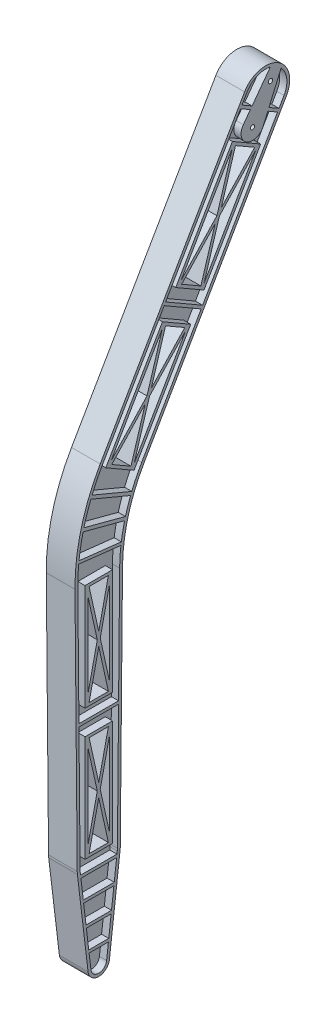
SolidWorks part; units mm, degrees
material "PET"
ref_plane "Front Plane" through (0, 0, 0) normal (0, 0, 1) x (1, 0, 0)
ref_plane "Top Plane" through (0, 0, 0) normal (0, 1, 0) x (1, 0, 0)
ref_plane "Right Plane" through (0, 0, 0) normal (1, 0, 0) x (0, 0, -1)
sketch "Sketch1" plane through (0, 0, 0) normal (1, 0, 0) x (0, 0, -1)
  line L0 (0, 0) -> (-155, -268.4679) construction
  line L1 (0, 0) -> (-19.4856, 11.25) construction
  line L2 (-155, -268.4679) -> (-174.4856, -257.2179) construction
  line L3 (-174.4856, -257.2179) -> (-19.4856, 11.25)
  line L4 (-19.4856, 11.25) -> (19.4856, -11.25) construction
  line L5 (-174.4856, -257.2179) -> (-135.5144, -279.7179) construction
  line L6 (-135.5144, -279.7179) -> (19.4856, -11.25)
  line L7 (-155, -268.4679) -> (-155, -538.4679) construction
  line L8 (-155, -538.4679) -> (-155, -558.4679) construction
  line L9 (-155, -558.4679) -> (-155, -623.0402) construction
  line L10 (-155, -538.4679) -> (-175, -538.4679) construction
  line L11 (-175, -538.4679) -> (-135, -538.4679) construction
  line L12 (-155, -268.4679) -> (-177.499, -268.2595) construction
  line L13 (-177.499, -268.2595) -> (-132.501, -268.6763) construction
  line L14 (-177.499, -268.2595) -> (-175, -538.4679)
  line L15 (-132.501, -268.6763) -> (-135, -538.4679)
  line L16 (-174.8597, -540.8327) -> (-164.9298, -624.2226)
  line L17 (-135.1403, -540.8327) -> (-145.0702, -624.2226)
  circle A0 centre (0, 0) radius 22.5
  circle A1 centre (-155, -268.4679) radius 22.5
  circle A2 centre (-155, -538.4679) radius 20
  circle A3 centre (-155, -623.0402) radius 10
  dimension "D1" = 45
  dimension "D3" = 45
  dimension "D4" = 155
  dimension "D6" = 40
  dimension "D7" = 20
  dimension "D2" = 310
  dimension "D5" = 270
  dimension "D8" = 150
  dimension "D10" = 84.5723
extrude "Boss-Extrude2" add sketch "Sketch1" along normal blind 20 contours A1 L15 L6 A0 L3 | A1 L6 L15 | A2 L15 L6 A1 L14 | L15 A1 L14 | A0 | A2 | A3 A2 | A3 region at (0, -134.2005, 77.4867) region at (0, -268.4679, 155) region at (0, 0, 0) region at (0, -274.433, 133.1432) region at (0, -402.5013, 155.0053) region at (0, -538.4679, 155) region at (0, -582.6002, 155) region at (0, -623.0402, 155)
fillet "Fillet1" radius 150 1 edges at (10, -274.5933, 132.5558)
fillet "Fillet2" radius 175 1 edges at (10, -268.2595, 177.499)
fillet "Fillet3" [suppressed] radius 50
sketch "Sketch2" plane through (20, 0, 0) normal (1, 0, 0) x (0, 0, -1)
  line L0 (0, 0) -> (11.25, 19.4856) construction
  line L1 (0, 0) -> (5.625, 9.7428) construction
  line L2 (5.625, 9.7428) -> (-6.375, -11.0418) construction
  circle A0 centre (0, 0) radius 22.5
  circle A1 centre (-6.375, -11.0418) radius 1.5
  dimension "D3" = 3
  dimension "D1" = 24
  dimension "D2" = 11.25
sketch "Sketch3" plane through (20, 0, 0) normal (1, 0, 0) x (0, 0, -1)
  circle A0 centre (5.625, 9.7428) radius 1.5
  circle A1 centre (-6.375, -11.0418) radius 1.5
  dimension "D1" = 3
  dimension "D2" = 3
extrude "Cut-Extrude1" cut sketch "Sketch3" against normal through all contours A0
extrude "Cut-Extrude3" cut sketch "Sketch2" against normal through all contours A1
sketch "Sketch4" plane through (20, 0, 0) normal (1, 0, 0) x (0, 0, -1)
  line L0 (-33.4856, -12.9987) -> (5.4856, -35.4987)
  line L1 (-153.6723, -221.1682) -> (-19.4856, 11.25) construction
  line L2 (-112.8314, -240.4297) -> (19.4856, -11.25) construction
  line L3 (-174.9649, -539.6524) -> (-135.0351, -539.6524)
  line L4 (-177.1103, -310.2866) -> (-175, -538.4679) construction
  line L5 (-177.1103, -310.2866) -> (-175, -538.4679)
  line L6 (-153.6723, -221.1682) -> (-33.4856, -12.9987)
  line L7 (-112.8314, -240.4297) -> (5.4856, -35.4987)
  line L8 (-132.9212, -314.0404) -> (-135, -538.4679) construction
  line L9 (-132.9212, -314.0404) -> (-135, -538.4679)
  arc A0 (19.4856, -11.25) -> (-19.4856, 11.25) centre (0, 0) ccw construction
  arc A1 (-175, -538.4679) -> (-174.8597, -540.8327) centre (-155, -538.4679) ccw construction
  arc A2 (-135.1403, -540.8327) -> (-135, -538.4679) centre (-155, -538.4679) ccw construction
  arc A3 (-153.6723, -221.1682) -> (-177.1103, -310.2866) centre (-2.1178, -308.6682) ccw construction
  arc A4 (-153.6723, -221.1682) -> (-177.1103, -310.2866) centre (-2.1178, -308.6682) ccw
  arc A5 (-112.8314, -240.4297) -> (-132.9212, -314.0404) centre (17.0724, -315.4297) ccw construction
  arc A6 (-112.8314, -240.4297) -> (-132.9212, -314.0404) centre (17.0724, -315.4297) ccw
  dimension "D1" = 28
sketch "Sketch5" plane through (20, 0, 0) normal (1, 0, 0) x (0, 0, -1)
  line L0 (-29.8253, -26.659) -> (-8.1747, -39.159)
  line L1 (-29.8253, -26.659) -> (-144.8253, -225.8448)
  line L2 (-8.1747, -39.159) -> (-123.1747, -238.3448)
  line L3 (-144.8253, -225.8448) -> (-123.1747, -238.3448)
  line L4 (-33.4856, -12.9987) -> (5.4856, -35.4987) construction
  line L5 (-112.8314, -240.4297) -> (5.4856, -35.4987) construction
  line L6 (-153.6723, -221.1682) -> (-33.4856, -12.9987) construction
  line L7 (-165.0811, -529.6524) -> (-144.9188, -529.6524)
  line L8 (-165.0811, -529.6524) -> (-165.0811, -314.6524)
  line L9 (-144.9188, -529.6524) -> (-144.9188, -314.6524)
  line L10 (-165.0811, -314.6524) -> (-144.9188, -314.6524)
  line L11 (-174.9649, -539.6524) -> (-135.0351, -539.6524) construction
  line L12 (-132.9212, -314.0404) -> (-135, -538.4679) construction
  line L13 (-177.1103, -310.2866) -> (-175, -538.4679) construction
  dimension "D1" = 10
  dimension "D2" = 10
  dimension "D3" = 10
  dimension "D4" = 230
  dimension "D5" = 10
  dimension "D6" = 10
  dimension "D7" = 10
  dimension "D8" = 215
extrude "Cut-Extrude4" cut sketch "Sketch5" against normal through all
sketch "Sketch6" plane through (20, 0, 0) normal (1, 0, 0) x (0, 0, -1)
  line L6 (-19.4856, 11.25) -> (-153.6723, -221.1682)
  line L7 (-177.1103, -310.2866) -> (-175, -538.4679)
  line L8 (-174.8597, -540.8327) -> (-164.9298, -624.2226)
  line L9 (-145.0702, -624.2226) -> (-135.1403, -540.8327)
  line L10 (-135, -538.4679) -> (-132.9212, -314.0404)
  line L11 (-112.8314, -240.4297) -> (19.4856, -11.25)
  line L12 (-19.4856, 11.25) -> (-153.6723, -221.1682)
  line L13 (-177.1103, -310.2866) -> (-175, -538.4679)
  line L14 (-174.8597, -540.8327) -> (-164.9298, -624.2226)
  line L15 (-145.0702, -624.2226) -> (-135.1403, -540.8327)
  line L16 (-135, -538.4679) -> (-132.9212, -314.0404)
  line L17 (-112.8314, -240.4297) -> (19.4856, -11.25)
  arc A6 (-153.6723, -221.1682) -> (-177.1103, -310.2866) centre (-2.1178, -308.6682) ccw
  arc A7 (-175, -538.4679) -> (-174.8597, -540.8327) centre (-155, -538.4679) ccw
  arc A8 (-164.9298, -624.2226) -> (-145.0702, -624.2226) centre (-155, -623.0402) ccw
  arc A9 (-135.1403, -540.8327) -> (-135, -538.4679) centre (-155, -538.4679) ccw
  arc A10 (-112.8314, -240.4297) -> (-132.9212, -314.0404) centre (17.0724, -315.4297) ccw
  arc A11 (19.4856, -11.25) -> (-19.4856, 11.25) centre (0, 0) ccw
  arc A12 (-153.6723, -221.1682) -> (-177.1103, -310.2866) centre (-2.1178, -308.6682) ccw
  arc A13 (-175, -538.4679) -> (-174.8597, -540.8327) centre (-155, -538.4679) ccw
  arc A14 (-164.9298, -624.2226) -> (-145.0702, -624.2226) centre (-155, -623.0402) ccw
  arc A15 (-135.1403, -540.8327) -> (-135, -538.4679) centre (-155, -538.4679) ccw
  arc A16 (-112.8314, -240.4297) -> (-132.9212, -314.0404) centre (17.0724, -315.4297) ccw
  arc A17 (19.4856, -11.25) -> (-19.4856, 11.25) centre (0, 0) ccw
  dimension "D1" = 0
scale "Scale1" scale about centroid uniform scaling yes scale factor 0.75
sketch "Sketch7" plane through (17.5, 0, 0) normal (1, 0, 0) x (0, 0, -1)
  line L0 (-42.9814, -81.6568) -> (-30.5187, -88.8521)
  line L1 (-42.9814, -81.6568) -> (-29.8288, -58.8759)
  line L2 (-30.5187, -88.8521) -> (-17.3662, -66.0713)
  line L3 (-29.8288, -58.8759) -> (-17.3662, -66.0713)
  line L4 (-143.9105, -238.1692) -> (-43.2705, -63.8556) construction
  line L5 (-34.7873, -101.6623) -> (-51.0253, -92.2873) construction
  dimension "D1" = 14.3906
  dimension "D2" = 26.3051
  dimension "D3" = 13.2282
  dimension "D4" = 9.151
extrude "Boss-Extrude3" add sketch "Sketch7" against normal through all
sketch "Sketch8" plane through (17.5, 0, 0) normal (1, 0, 0) x (0, 0, -1)
  line L0 (-42.9063, -96.9748) -> (-20.2188, -57.6789) construction
  line L1 (-34.7873, -101.6623) -> (-51.0253, -92.2873) construction
  circle A0 centre (-25.2188, -66.3391) radius 1.5
  circle A1 centre (-37.7188, -87.9898) radius 1.5
  arc A2 (-14.0421, -80.7306) -> (-43.2705, -63.8556) centre (-28.6563, -72.2931) ccw construction
  dimension "D3" = 3
  dimension "D4" = 3
  dimension "D1" = 25
  dimension "D2" = 10
extrude "Cut-Extrude5" cut sketch "Sketch8" against normal through all
sketch "Sketch9" plane through (0, 2.7728, 4.8026) normal (0, 0.5, 0.866) x (1, 0, 0)
  line L0 (17.5, -278.2159) -> (17.5, -76.9358) construction
  line L1 (17.5, -60.0608) -> (12.5, -60.0608)
  line L2 (17.5, -60.0608) -> (17.5, -547.2373)
  line L3 (17.5, -547.2373) -> (12.5, -547.2373)
  line L4 (12.5, -60.0608) -> (12.5, -547.2373)
  line L5 (2.5, -278.2159) -> (2.5, -76.9358) construction
  line L6 (17.5, -60.0608) -> (2.5, -60.0608) construction
  line L7 (2.5, -547.2373) -> (17.5, -547.2373) construction
  dimension "D1" = 10
extrude "Cut-Extrude6" cut sketch "Sketch9" against normal through all
sketch "Sketch11" plane through (12.5, 0, 0) normal (1, 0, 0) x (0, 0, -1)
  line L0 (-137.2753, -241.6767) -> (-121.0373, -251.0517)
  line L1 (-137.2753, -241.6767) -> (-51.0253, -92.2873)
  line L2 (-121.0373, -251.0517) -> (-34.7873, -101.6623)
  line L3 (-51.0253, -92.2873) -> (-34.7873, -101.6623)
  line L4 (-34.7873, -101.6623) -> (-51.0253, -92.2873) construction
  line L5 (-152.4672, -308.2823) -> (-137.3454, -308.2823)
  line L6 (-152.4672, -308.2823) -> (-152.4672, -469.5323)
  line L7 (-137.3454, -308.2823) -> (-137.3454, -469.5323)
  line L8 (-152.4672, -469.5323) -> (-137.3454, -469.5323)
  line L9 (-152.4672, -469.5323) -> (-137.3454, -469.5323) construction
extrude "Boss-Extrude4" add sketch "Sketch11" against normal blind 10
sketch "Sketch13" plane through (12.5, 0, 0) normal (1, 0, 0) x (0, 0, -1)
  line L0 (-137.2753, -241.6767) -> (-121.0373, -251.0517)
  line L1 (-137.2753, -241.6767) -> (-99.7753, -176.7248)
  line L2 (-121.0373, -251.0517) -> (-83.5373, -186.0998)
  line L3 (-99.7753, -176.7248) -> (-83.5373, -186.0998)
  line L4 (-152.4672, -399.5323) -> (-137.3454, -399.5323)
  line L5 (-152.4672, -399.5323) -> (-152.4672, -469.5323)
  line L6 (-137.3454, -399.5323) -> (-137.3454, -469.5323)
  line L7 (-152.4672, -469.5323) -> (-137.3454, -469.5323)
  line L9 (-152.4672, -469.5323) -> (-137.3454, -469.5323) construction
  line L10 (-152.4672, -308.2823) -> (-152.4672, -469.5323) construction
  line L11 (-137.3454, -308.2823) -> (-137.3454, -469.5323) construction
  line L13 (-137.2753, -241.6767) -> (-51.0253, -92.2873) construction
  line L16 (-121.0373, -251.0517) -> (-34.7873, -101.6623) construction
  line L17 (-137.2753, -241.6767) -> (-121.0373, -251.0517) construction
  line L18 (-51.0253, -92.2873) -> (-34.7873, -101.6623)
  line L19 (-51.0253, -92.2873) -> (-88.5253, -157.2392)
  line L20 (-34.7873, -101.6623) -> (-72.2873, -166.6142)
  line L21 (-88.5253, -157.2392) -> (-72.2873, -166.6142)
  line L22 (-152.4672, -308.2823) -> (-137.3454, -308.2823)
  line L23 (-152.4672, -308.2823) -> (-152.4672, -378.2823)
  line L24 (-137.3454, -308.2823) -> (-137.3454, -378.2823)
  line L25 (-152.4672, -378.2823) -> (-137.3454, -378.2823)
  dimension "D1" = 75
  dimension "D2" = 75
  dimension "D3" = 70
  dimension "D4" = 70
extrude "Cut-Extrude7" cut sketch "Sketch13" against normal blind 10
ref_plane "Plane1" through (0, -450.9942, -148.3609) normal (0, -0.9499, -0.3125) x (-1, 0, 0)
sketch "Sketch15" plane through (12.5, 0, 0) normal (1, 0, 0) x (0, 0, -1)
  line L0 (-25.2188, -66.3391) -> (-37.7188, -87.9898) construction
  point P4 (0, 0)
ref_plane "Plane2" through (0, -13.4953, 41.0235) normal (0, -0.3125, 0.9499) x (1, 0, 0)
sketch "Sketch16" plane through (12.5, 0, 0) normal (1, 0, 0) x (0, 0, -1)
  line L0 (-144.9063, -547.0732) -> (-153.3569, -521.3847) construction
  line L1 (140.524, -453.5723) -> (156.1977, -448.4162) construction
  arc A0 (-152.3537, -540.46) -> (-137.4589, -540.46) centre (-144.9063, -539.5732) ccw construction
  dimension "D1" = 90
  dimension "D2" = 27.0428
sketch "Sketch18" plane through (2.5, 0, 0) normal (-1, 0, 0) x (0, 0, 1)
  line L0 (88.5253, -157.2392) -> (72.2873, -166.6142) construction
  line L1 (72.2873, -166.6142) -> (34.7873, -101.6623) construction
  line L2 (51.0253, -92.2873) -> (88.5253, -157.2392) construction
  line L3 (34.7873, -101.6623) -> (51.0253, -92.2873) construction
  line L4 (88.5253, -157.2392) -> (72.2873, -166.6142)
  line L5 (72.2873, -166.6142) -> (34.7873, -101.6623)
  line L6 (159.9063, -476.144) -> (161.4891, -305.008)
  line L7 (143.9105, -238.1692) -> (43.2705, -63.8556)
  line L8 (14.0421, -80.7306) -> (113.2799, -252.6154)
  line L9 (128.3472, -307.8233) -> (129.9063, -476.144)
  line L10 (130.0116, -477.9176) -> (137.4589, -540.46)
  line L11 (152.3537, -540.46) -> (159.8011, -477.9176)
  line L12 (159.9063, -476.144) -> (161.4891, -305.008)
  line L13 (143.9105, -238.1692) -> (43.2705, -63.8556)
  line L14 (14.0421, -80.7306) -> (113.2799, -252.6154)
  line L15 (128.3472, -307.8233) -> (129.9063, -476.144)
  line L16 (130.0116, -477.9176) -> (137.4589, -540.46)
  line L17 (152.3537, -540.46) -> (159.8011, -477.9176)
  line L18 (51.0253, -92.2873) -> (88.5253, -157.2392)
  line L19 (34.7873, -101.6623) -> (51.0253, -92.2873)
  line L20 (137.2753, -241.6767) -> (121.0373, -251.0517) construction
  line L21 (99.7753, -176.7248) -> (137.2753, -241.6767) construction
  line L22 (121.0373, -251.0517) -> (83.5373, -186.0998) construction
  line L23 (83.5373, -186.0998) -> (99.7753, -176.7248) construction
  line L24 (137.2753, -241.6767) -> (121.0373, -251.0517)
  line L25 (99.7753, -176.7248) -> (137.2753, -241.6767)
  line L26 (121.0373, -251.0517) -> (83.5373, -186.0998)
  line L27 (83.5373, -186.0998) -> (99.7753, -176.7248)
  line L28 (137.3454, -308.2823) -> (152.4672, -308.2823) construction
  line L29 (152.4672, -308.2823) -> (152.4672, -378.2823) construction
  line L30 (137.3454, -378.2823) -> (137.3454, -308.2823) construction
  line L31 (152.4672, -378.2823) -> (137.3454, -378.2823) construction
  line L32 (152.4672, -378.2823) -> (137.3454, -378.2823)
  line L33 (137.3454, -378.2823) -> (137.3454, -308.2823)
  line L34 (152.4672, -308.2823) -> (152.4672, -378.2823)
  line L35 (137.3454, -308.2823) -> (152.4672, -308.2823)
  line L36 (152.4672, -469.5323) -> (137.3454, -469.5323) construction
  line L37 (152.4672, -399.5323) -> (152.4672, -469.5323) construction
  line L38 (137.3454, -469.5323) -> (137.3454, -399.5323) construction
  line L39 (137.3454, -399.5323) -> (152.4672, -399.5323) construction
  line L40 (152.4672, -469.5323) -> (137.3454, -469.5323)
  line L41 (152.4672, -399.5323) -> (152.4672, -469.5323)
  line L42 (137.3454, -469.5323) -> (137.3454, -399.5323)
  line L43 (137.3454, -399.5323) -> (152.4672, -399.5323)
  circle A0 centre (25.2188, -66.3391) radius 1.5 construction
  circle A1 centre (37.7188, -87.9898) radius 1.5 construction
  circle A2 centre (25.2188, -66.3391) radius 1.5
  circle A3 centre (37.7188, -87.9898) radius 1.5
  arc A6 (161.4891, -305.008) -> (143.9105, -238.1692) centre (30.2447, -303.7942) ccw
  arc A7 (43.2705, -63.8556) -> (14.0421, -80.7306) centre (28.6563, -72.2931) ccw
  arc A8 (128.3472, -307.8233) -> (113.2799, -252.6154) centre (15.852, -308.8654) ccw
  arc A9 (129.9063, -476.144) -> (130.0116, -477.9176) centre (144.9063, -476.144) ccw
  arc A10 (137.4589, -540.46) -> (152.3537, -540.46) centre (144.9063, -539.5732) ccw
  arc A11 (159.8011, -477.9176) -> (159.9063, -476.144) centre (144.9063, -476.144) ccw
  arc A12 (161.4891, -305.008) -> (143.9105, -238.1692) centre (30.2447, -303.7942) ccw
  arc A13 (43.2705, -63.8556) -> (14.0421, -80.7306) centre (28.6563, -72.2931) ccw
  arc A14 (128.3472, -307.8233) -> (113.2799, -252.6154) centre (15.852, -308.8654) ccw
  arc A15 (129.9063, -476.144) -> (130.0116, -477.9176) centre (144.9063, -476.144) ccw
  arc A16 (137.4589, -540.46) -> (152.3537, -540.46) centre (144.9063, -539.5732) ccw
  arc A17 (159.8011, -477.9176) -> (159.9063, -476.144) centre (144.9063, -476.144) ccw
  dimension "D1" = 0
extrude "Boss-Extrude5" add sketch "Sketch18" along normal blind 5
sketch "Sketch19" plane through (-2.5, 0, 0) normal (-1, 0, 0) x (0, 0, 1)
  line L46 (131.9975, -477.6811) -> (139.4449, -540.2236)
  line L47 (150.3677, -540.2236) -> (157.8151, -477.6811)
  line L48 (157.9063, -476.1351) -> (159.4892, -304.9895)
  line L49 (130.3471, -307.8048) -> (131.9063, -476.135)
  line L50 (142.1785, -239.1692) -> (41.5385, -64.8556)
  line L51 (15.7742, -79.7306) -> (115.0119, -251.6154)
  line L52 (131.9975, -477.6811) -> (139.4449, -540.2236)
  line L53 (150.3677, -540.2236) -> (157.8151, -477.6811)
  line L54 (157.9063, -476.1351) -> (159.4892, -304.9895)
  line L55 (130.3471, -307.8048) -> (131.9063, -476.135)
  line L56 (142.1785, -239.1692) -> (41.5385, -64.8556)
  line L57 (15.7742, -79.7306) -> (115.0119, -251.6154)
  line L60 (71.5553, -169.3462) -> (91.2574, -157.9712)
  line L61 (32.0553, -100.9302) -> (71.5553, -169.3462)
  line L62 (91.2574, -157.9712) -> (51.7574, -89.5552)
  line L63 (51.7574, -89.5552) -> (32.0553, -100.9302)
  line L64 (71.5553, -169.3462) -> (91.2574, -157.9712)
  line L65 (32.0553, -100.9302) -> (71.5553, -169.3462)
  line L66 (91.2574, -157.9712) -> (51.7574, -89.5552)
  line L67 (51.7574, -89.5552) -> (32.0553, -100.9302)
  line L72 (100.5074, -173.9927) -> (80.8053, -185.3677)
  line L73 (80.8053, -185.3677) -> (120.3053, -253.7837)
  line L74 (140.0074, -242.4087) -> (100.5074, -173.9927)
  line L75 (120.3053, -253.7837) -> (140.0074, -242.4087)
  line L76 (100.5074, -173.9927) -> (80.8053, -185.3677)
  line L77 (80.8053, -185.3677) -> (120.3053, -253.7837)
  line L78 (140.0074, -242.4087) -> (100.5074, -173.9927)
  line L79 (120.3053, -253.7837) -> (140.0074, -242.4087)
  line L84 (154.4672, -306.2823) -> (135.3454, -306.2823)
  line L85 (154.4672, -380.2823) -> (154.4672, -306.2823)
  line L86 (135.3454, -306.2823) -> (135.3454, -380.2823)
  line L87 (135.3454, -380.2823) -> (154.4672, -380.2823)
  line L88 (154.4672, -306.2823) -> (135.3454, -306.2823)
  line L89 (154.4672, -380.2823) -> (154.4672, -306.2823)
  line L90 (135.3454, -306.2823) -> (135.3454, -380.2823)
  line L91 (135.3454, -380.2823) -> (154.4672, -380.2823)
  line L96 (154.4672, -471.5323) -> (154.4672, -397.5323)
  line L97 (135.3454, -471.5323) -> (154.4672, -471.5323)
  line L98 (135.3454, -397.5323) -> (135.3454, -471.5323)
  line L99 (154.4672, -397.5323) -> (135.3454, -397.5323)
  line L100 (154.4672, -471.5323) -> (154.4672, -397.5323)
  line L101 (135.3454, -471.5323) -> (154.4672, -471.5323)
  line L102 (135.3454, -397.5323) -> (135.3454, -471.5323)
  line L103 (154.4672, -397.5323) -> (135.3454, -397.5323)
  arc A46 (139.4449, -540.2236) -> (150.3677, -540.2236) centre (144.9063, -539.5732) ccw
  arc A47 (157.8151, -477.6811) -> (157.9063, -476.1351) centre (144.9063, -476.144) ccw
  arc A48 (131.9063, -476.135) -> (131.9975, -477.6811) centre (144.9063, -476.144) ccw
  arc A49 (159.4892, -304.9895) -> (142.1785, -239.1692) centre (30.2447, -303.7942) ccw
  arc A50 (130.3471, -307.8048) -> (115.0119, -251.6154) centre (15.852, -308.8654) ccw
  arc A51 (41.5385, -64.8556) -> (15.7742, -79.7306) centre (28.6563, -72.2931) ccw
  arc A52 (139.4449, -540.2236) -> (150.3677, -540.2236) centre (144.9063, -539.5732) ccw
  arc A53 (157.8151, -477.6811) -> (157.9063, -476.1351) centre (144.9063, -476.144) ccw
  arc A54 (131.9063, -476.135) -> (131.9975, -477.6811) centre (144.9063, -476.144) ccw
  arc A55 (159.4892, -304.9895) -> (142.1785, -239.1692) centre (30.2447, -303.7942) ccw
  arc A56 (130.3471, -307.8048) -> (115.0119, -251.6154) centre (15.852, -308.8654) ccw
  arc A57 (41.5385, -64.8556) -> (15.7742, -79.7306) centre (28.6563, -72.2931) ccw
  circle A61 centre (25.2188, -66.3391) radius 3.5
  circle A62 centre (25.2188, -66.3391) radius 3.5
  circle A64 centre (37.7188, -87.9898) radius 3.5
  circle A65 centre (37.7188, -87.9898) radius 3.5
  dimension "D1" = 2
  dimension "D2" = 2
  dimension "D3" = 2
  dimension "D4" = 2
  dimension "D5" = 2
  dimension "D6" = 2
  dimension "D7" = 2
extrude "Cut-Extrude8" cut sketch "Sketch19" against normal blind 5
sketch "Sketch21" plane through (12.5, 0, 0) normal (1, 0, 0) x (0, 0, -1)
  line L0 (-137.2753, -241.6767) -> (-121.0373, -251.0517) construction
  line L1 (-99.7753, -176.7248) -> (-137.2753, -241.6767) construction
  line L2 (-121.0373, -251.0517) -> (-83.5373, -186.0998) construction
  line L3 (-83.5373, -186.0998) -> (-99.7753, -176.7248) construction
  line L4 (-137.2753, -241.6767) -> (-121.0373, -251.0517)
  line L5 (-99.7753, -176.7248) -> (-137.2753, -241.6767)
  line L6 (-43.2705, -63.8556) -> (-143.9105, -238.1692)
  line L7 (-161.4891, -305.008) -> (-159.9063, -476.144)
  line L8 (-159.8011, -477.9176) -> (-152.3537, -540.46)
  line L9 (-137.4589, -540.46) -> (-130.0116, -477.9176)
  line L10 (-129.9063, -476.144) -> (-128.3472, -307.8233)
  line L11 (-113.2799, -252.6154) -> (-14.0421, -80.7306)
  line L12 (-43.2705, -63.8556) -> (-143.9105, -238.1692)
  line L13 (-161.4891, -305.008) -> (-159.9063, -476.144)
  line L14 (-159.8011, -477.9176) -> (-152.3537, -540.46)
  line L15 (-137.4589, -540.46) -> (-130.0116, -477.9176)
  line L16 (-129.9063, -476.144) -> (-128.3472, -307.8233)
  line L17 (-113.2799, -252.6154) -> (-14.0421, -80.7306)
  line L18 (-121.0373, -251.0517) -> (-83.5373, -186.0998)
  line L19 (-83.5373, -186.0998) -> (-99.7753, -176.7248)
  line L20 (-72.2873, -166.6142) -> (-34.7873, -101.6623) construction
  line L21 (-51.0253, -92.2873) -> (-88.5253, -157.2392) construction
  line L22 (-34.7873, -101.6623) -> (-51.0253, -92.2873) construction
  line L23 (-88.5253, -157.2392) -> (-72.2873, -166.6142) construction
  line L24 (-88.5253, -157.2392) -> (-72.2873, -166.6142)
  line L25 (-72.2873, -166.6142) -> (-34.7873, -101.6623)
  line L26 (-34.7873, -101.6623) -> (-51.0253, -92.2873)
  line L27 (-51.0253, -92.2873) -> (-88.5253, -157.2392)
  line L28 (-152.4672, -308.2823) -> (-152.4672, -378.2823) construction
  line L29 (-137.3454, -378.2823) -> (-137.3454, -308.2823) construction
  line L30 (-152.4672, -378.2823) -> (-137.3454, -378.2823) construction
  line L31 (-137.3454, -308.2823) -> (-152.4672, -308.2823) construction
  line L32 (-152.4672, -378.2823) -> (-137.3454, -378.2823)
  line L33 (-137.3454, -378.2823) -> (-137.3454, -308.2823)
  line L34 (-137.3454, -308.2823) -> (-152.4672, -308.2823)
  line L35 (-152.4672, -308.2823) -> (-152.4672, -378.2823)
  line L36 (-137.3454, -399.5323) -> (-152.4672, -399.5323) construction
  line L37 (-152.4672, -399.5323) -> (-152.4672, -469.5323) construction
  line L38 (-137.3454, -469.5323) -> (-137.3454, -399.5323) construction
  line L39 (-152.4672, -469.5323) -> (-137.3454, -469.5323) construction
  line L40 (-137.3454, -399.5323) -> (-152.4672, -399.5323)
  line L41 (-152.4672, -399.5323) -> (-152.4672, -469.5323)
  line L42 (-137.3454, -469.5323) -> (-137.3454, -399.5323)
  line L43 (-152.4672, -469.5323) -> (-137.3454, -469.5323)
  circle A0 centre (-25.2188, -66.3391) radius 1.5 construction
  circle A1 centre (-37.7188, -87.9898) radius 1.5 construction
  circle A2 centre (-25.2188, -66.3391) radius 1.5
  circle A3 centre (-37.7188, -87.9898) radius 1.5
  arc A6 (-143.9105, -238.1692) -> (-161.4891, -305.008) centre (-30.2447, -303.7942) ccw
  arc A7 (-159.9063, -476.144) -> (-159.8011, -477.9176) centre (-144.9063, -476.144) ccw
  arc A8 (-152.3537, -540.46) -> (-137.4589, -540.46) centre (-144.9063, -539.5732) ccw
  arc A9 (-130.0116, -477.9176) -> (-129.9063, -476.144) centre (-144.9063, -476.144) ccw
  arc A10 (-113.2799, -252.6154) -> (-128.3472, -307.8233) centre (-15.852, -308.8654) ccw
  arc A11 (-14.0421, -80.7306) -> (-43.2705, -63.8556) centre (-28.6563, -72.2931) ccw
  arc A12 (-143.9105, -238.1692) -> (-161.4891, -305.008) centre (-30.2447, -303.7942) ccw
  arc A13 (-159.9063, -476.144) -> (-159.8011, -477.9176) centre (-144.9063, -476.144) ccw
  arc A14 (-152.3537, -540.46) -> (-137.4589, -540.46) centre (-144.9063, -539.5732) ccw
  arc A15 (-130.0116, -477.9176) -> (-129.9063, -476.144) centre (-144.9063, -476.144) ccw
  arc A16 (-113.2799, -252.6154) -> (-128.3472, -307.8233) centre (-15.852, -308.8654) ccw
  arc A17 (-14.0421, -80.7306) -> (-43.2705, -63.8556) centre (-28.6563, -72.2931) ccw
  dimension "D1" = 0
extrude "Boss-Extrude6" add sketch "Sketch21" along normal blind 5
sketch "Sketch22" plane through (17.5, 0, 0) normal (1, 0, 0) x (0, 0, -1)
  line L45 (-157.8151, -477.6811) -> (-150.3677, -540.2236)
  line L46 (-139.4449, -540.2236) -> (-131.9975, -477.6811)
  line L47 (-131.9063, -476.135) -> (-130.3471, -307.8048)
  line L48 (-159.4892, -304.9895) -> (-157.9063, -476.1351)
  line L49 (-115.0119, -251.6154) -> (-15.7742, -79.7306)
  line L50 (-41.5385, -64.8556) -> (-142.1785, -239.1692)
  line L51 (-157.8151, -477.6811) -> (-150.3677, -540.2236)
  line L52 (-139.4449, -540.2236) -> (-131.9975, -477.6811)
  line L53 (-131.9063, -476.135) -> (-130.3471, -307.8048)
  line L54 (-159.4892, -304.9895) -> (-157.9063, -476.1351)
  line L55 (-115.0119, -251.6154) -> (-15.7742, -79.7306)
  line L56 (-41.5385, -64.8556) -> (-142.1785, -239.1692)
  line L65 (-91.2574, -157.9712) -> (-71.5553, -169.3462)
  line L66 (-71.5553, -169.3462) -> (-32.0553, -100.9302)
  line L67 (-32.0553, -100.9302) -> (-51.7574, -89.5552)
  line L68 (-51.7574, -89.5552) -> (-91.2574, -157.9712)
  line L69 (-91.2574, -157.9712) -> (-71.5553, -169.3462)
  line L70 (-71.5553, -169.3462) -> (-32.0553, -100.9302)
  line L71 (-32.0553, -100.9302) -> (-51.7574, -89.5552)
  line L72 (-51.7574, -89.5552) -> (-91.2574, -157.9712)
  line L83 (-140.0074, -242.4087) -> (-120.3053, -253.7837)
  line L84 (-100.5074, -173.9927) -> (-140.0074, -242.4087)
  line L85 (-120.3053, -253.7837) -> (-80.8053, -185.3677)
  line L86 (-80.8053, -185.3677) -> (-100.5074, -173.9927)
  line L87 (-140.0074, -242.4087) -> (-120.3053, -253.7837)
  line L88 (-100.5074, -173.9927) -> (-140.0074, -242.4087)
  line L89 (-120.3053, -253.7837) -> (-80.8053, -185.3677)
  line L90 (-80.8053, -185.3677) -> (-100.5074, -173.9927)
  line L104 (-154.4672, -380.2823) -> (-135.3454, -380.2823)
  line L105 (-154.4672, -306.2823) -> (-154.4672, -380.2823)
  line L106 (-135.3454, -306.2823) -> (-154.4672, -306.2823)
  line L107 (-135.3454, -380.2823) -> (-135.3454, -306.2823)
  line L108 (-154.4672, -380.2823) -> (-135.3454, -380.2823)
  line L109 (-154.4672, -306.2823) -> (-154.4672, -380.2823)
  line L110 (-135.3454, -306.2823) -> (-154.4672, -306.2823)
  line L111 (-135.3454, -380.2823) -> (-135.3454, -306.2823)
  line L122 (-154.4672, -471.5323) -> (-135.3454, -471.5323)
  line L123 (-135.3454, -471.5323) -> (-135.3454, -397.5323)
  line L124 (-135.3454, -397.5323) -> (-154.4672, -397.5323)
  line L125 (-154.4672, -397.5323) -> (-154.4672, -471.5323)
  line L126 (-154.4672, -471.5323) -> (-135.3454, -471.5323)
  line L127 (-135.3454, -471.5323) -> (-135.3454, -397.5323)
  line L128 (-135.3454, -397.5323) -> (-154.4672, -397.5323)
  line L129 (-154.4672, -397.5323) -> (-154.4672, -471.5323)
  arc A45 (-150.3677, -540.2236) -> (-139.4449, -540.2236) centre (-144.9063, -539.5732) ccw
  arc A46 (-131.9975, -477.6811) -> (-131.9063, -476.135) centre (-144.9063, -476.144) ccw
  arc A47 (-157.9063, -476.1351) -> (-157.8151, -477.6811) centre (-144.9063, -476.144) ccw
  arc A48 (-115.0119, -251.6154) -> (-130.3471, -307.8048) centre (-15.852, -308.8654) ccw
  arc A49 (-142.1785, -239.1692) -> (-159.4892, -304.9895) centre (-30.2447, -303.7942) ccw
  arc A50 (-15.7742, -79.7306) -> (-41.5385, -64.8556) centre (-28.6563, -72.2931) ccw
  arc A51 (-150.3677, -540.2236) -> (-139.4449, -540.2236) centre (-144.9063, -539.5732) ccw
  arc A52 (-131.9975, -477.6811) -> (-131.9063, -476.135) centre (-144.9063, -476.144) ccw
  arc A53 (-157.9063, -476.1351) -> (-157.8151, -477.6811) centre (-144.9063, -476.144) ccw
  arc A54 (-115.0119, -251.6154) -> (-130.3471, -307.8048) centre (-15.852, -308.8654) ccw
  arc A55 (-142.1785, -239.1692) -> (-159.4892, -304.9895) centre (-30.2447, -303.7942) ccw
  arc A56 (-15.7742, -79.7306) -> (-41.5385, -64.8556) centre (-28.6563, -72.2931) ccw
  circle A59 centre (-25.2188, -66.3391) radius 3.5
  circle A60 centre (-25.2188, -66.3391) radius 3.5
  circle A62 centre (-37.7188, -87.9898) radius 3.5
  circle A63 centre (-37.7188, -87.9898) radius 3.5
  dimension "D1" = 2
  dimension "D2" = 2
  dimension "D3" = 2
  dimension "D4" = 2
  dimension "D5" = 2
  dimension "D6" = 2
  dimension "D7" = 2
extrude "Cut-Extrude9" cut sketch "Sketch22" against normal blind 5
sketch "Sketch24" plane through (12.5, 0, 0) normal (1, 0, 0) x (0, 0, -1)
  line L0 (-46.0385, -72.6498) -> (-20.2742, -87.5248)
  line L1 (-41.5385, -64.8556) -> (-142.1785, -239.1692) construction
  line L2 (-115.0119, -251.6154) -> (-15.7742, -79.7306) construction
  line L3 (-45.0385, -70.9177) -> (-19.2742, -85.7927)
  line L4 (-41.5385, -64.8556) -> (-142.1785, -239.1692) construction
  line L5 (-32.0553, -100.9302) -> (-51.7574, -89.5552) construction
  line L6 (-155.3388, -271.2823) -> (-126.3395, -278.8193)
  line L7 (-156.5965, -276.1216) -> (-154.0811, -266.4431) construction
  line L8 (-135.3454, -306.2823) -> (-154.4672, -306.2823) construction
  line L9 (-155.8269, -273.2219) -> (-126.8474, -280.7537)
  line L10 (-45.0385, -70.9177) -> (-46.0385, -72.6498)
  line L11 (-20.2742, -87.5248) -> (-19.2742, -85.7927)
  line L12 (-98.2885, -163.1495) -> (-72.5242, -178.0245)
  line L13 (-115.0119, -251.6154) -> (-15.7742, -79.7306) construction
  line L14 (-99.2885, -164.8815) -> (-73.5242, -179.7565)
  line L15 (-159.2388, -294.2507) -> (-158.1161, -284.314) construction
  line L16 (-91.2574, -157.9712) -> (-71.5553, -169.3462) construction
  line L17 (-99.2885, -164.8815) -> (-98.2885, -163.1495)
  line L18 (-72.5242, -178.0245) -> (-73.5242, -179.7565)
  line L19 (-158.6774, -289.2823) -> (-129.1928, -292.6139)
  line L20 (-158.8866, -291.2714) -> (-129.4595, -294.5965)
  line L21 (-151.5507, -258.9009) -> (-147.72, -249.6638) construction
  line L22 (-149.6354, -254.2823) -> (-121.9327, -265.7708)
  line L23 (-150.3872, -256.1357) -> (-122.6693, -267.6305)
  line L24 (-158.7073, -389.5323) -> (-131.1041, -389.5323)
  line L25 (-138.1718, -529.5323) -> (-137.9337, -527.5323)
  line L26 (-150.3872, -256.1357) -> (-149.6354, -254.2823)
  line L27 (-159.4892, -304.9895) -> (-157.9063, -476.1351) construction
  line L28 (-131.9063, -476.135) -> (-130.3471, -307.8048) construction
  line L29 (-135.3454, -397.5323) -> (-154.4672, -397.5323) construction
  line L30 (-158.7258, -387.5323) -> (-131.0856, -387.5323)
  line L31 (-158.7073, -389.5323) -> (-158.7258, -387.5323)
  line L32 (-131.1041, -389.5323) -> (-131.0856, -387.5323)
  line L33 (-157.5947, -479.5323) -> (-132.218, -479.5323)
  line L34 (-157.8151, -477.6811) -> (-150.3677, -540.2236) construction
  line L35 (-139.4449, -540.2236) -> (-131.9975, -477.6811) construction
  line L36 (-157.3565, -481.5323) -> (-132.4561, -481.5323)
  line L37 (-157.8151, -477.6811) -> (-150.3677, -540.2236) construction
  line L38 (-154.4672, -471.5323) -> (-135.3454, -471.5323) construction
  line L39 (-157.3565, -481.5323) -> (-157.5947, -479.5323)
  line L40 (-132.4561, -481.5323) -> (-132.218, -479.5323)
  line L41 (-155.6895, -495.5323) -> (-134.1232, -495.5323)
  line L42 (-155.4513, -497.5323) -> (-134.3614, -497.5323)
  line L43 (-154.4672, -471.5323) -> (-135.3454, -471.5323) construction
  line L44 (-155.4513, -497.5323) -> (-155.6895, -495.5323)
  line L45 (-134.3614, -497.5323) -> (-134.1232, -495.5323)
  line L46 (-153.7842, -511.5323) -> (-136.0284, -511.5323)
  line L47 (-139.4449, -540.2236) -> (-131.9975, -477.6811) construction
  line L48 (-153.5461, -513.5323) -> (-136.2666, -513.5323)
  line L49 (-153.5461, -513.5323) -> (-153.7842, -511.5323)
  line L50 (-136.2666, -513.5323) -> (-136.0284, -511.5323)
  line L51 (-151.6408, -529.5323) -> (-138.1718, -529.5323)
  line L52 (-151.879, -527.5323) -> (-137.9337, -527.5323)
  line L53 (-151.6408, -529.5323) -> (-151.879, -527.5323)
  line L54 (-121.9327, -265.7708) -> (-121.009, -266.1539)
  line L55 (-122.6693, -267.6305) -> (-121.7751, -268.0013)
  line L56 (-121.7751, -268.0013) -> (-121.009, -266.1539)
  line L57 (-155.8269, -273.2219) -> (-155.3388, -271.2823)
  line L58 (-126.3395, -278.8193) -> (-125.3717, -279.0708)
  line L59 (-126.8474, -280.7537) -> (-125.8747, -281.0065)
  line L60 (-125.3717, -279.0708) -> (-125.8747, -281.0065)
  line L61 (-129.1928, -292.6139) -> (-128.2412, -292.7214)
  line L62 (-129.4595, -294.5965) -> (-128.4658, -294.7087)
  line L63 (-158.8866, -291.2714) -> (-158.6774, -289.2823)
  line L64 (-128.4658, -294.7087) -> (-128.2412, -292.7214)
  arc A0 (-142.1785, -239.1692) -> (-159.4892, -304.9895) centre (-30.2447, -303.7942) ccw construction
  arc A1 (-115.0119, -251.6154) -> (-130.3471, -307.8048) centre (-15.852, -308.8654) ccw construction
  arc A4 (-142.1785, -239.1692) -> (-159.4892, -304.9895) centre (-30.2447, -303.7942) ccw construction
  arc A10 (-115.0119, -251.6154) -> (-130.3471, -307.8048) centre (-15.852, -308.8654) ccw construction
  point P23 (-155.3388, -271.2823)
  point P48 (-158.6774, -289.2823)
  point P50 (-149.6354, -254.2823)
  dimension "D14" = 8
  dimension "D1" = 2
  dimension "D2" = 17.5
  dimension "D3" = 10
  dimension "D4" = 35
  dimension "D5" = 2
  dimension "D6" = 2
  dimension "D7" = 8
  dimension "D8" = 10
  dimension "D9" = 17
  dimension "D10" = 2
  dimension "D11" = 10
  dimension "D12" = 52
  dimension "D13" = 2
  dimension "D15" = 2
  dimension "D16" = 2
  dimension "D17" = 8
  dimension "D18" = 2
  dimension "D19" = 24
  dimension "D20" = 2
  dimension "D21" = 40
  dimension "D22" = 2
  dimension "D23" = 56
  dimension "D24" = 1
  dimension "D25" = 1
  dimension "D26" = 1
sketch "Sketch25" plane through (17.5, 0, 0) normal (1, 0, 0) x (0, 0, -1)
  line L0 (-72.5242, -178.0245) -> (-73.5242, -179.7565) construction
  line L1 (-99.2885, -164.8815) -> (-73.5242, -179.7565) construction
  line L2 (-98.2885, -163.1495) -> (-72.5242, -178.0245) construction
  line L3 (-99.2885, -164.8815) -> (-98.2885, -163.1495) construction
  line L4 (-72.5242, -178.0245) -> (-73.5242, -179.7565)
  line L5 (-99.2885, -164.8815) -> (-73.5242, -179.7565)
  line L6 (-98.2885, -163.1495) -> (-72.5242, -178.0245)
  line L7 (-99.2885, -164.8815) -> (-98.2885, -163.1495)
  line L8 (-20.2742, -87.5248) -> (-19.2742, -85.7927) construction
  line L9 (-45.0385, -70.9177) -> (-46.0385, -72.6498) construction
  line L10 (-45.0385, -70.9177) -> (-19.2742, -85.7927) construction
  line L11 (-46.0385, -72.6498) -> (-20.2742, -87.5248) construction
  line L12 (-20.2742, -87.5248) -> (-19.2742, -85.7927)
  line L13 (-45.0385, -70.9177) -> (-46.0385, -72.6498)
  line L14 (-45.0385, -70.9177) -> (-19.2742, -85.7927)
  line L15 (-46.0385, -72.6498) -> (-20.2742, -87.5248)
  line L16 (-131.1041, -389.5323) -> (-131.0856, -387.5323) construction
  line L17 (-158.7073, -389.5323) -> (-158.7258, -387.5323) construction
  line L18 (-158.7258, -387.5323) -> (-131.0856, -387.5323) construction
  line L19 (-158.7073, -389.5323) -> (-131.1041, -389.5323) construction
  line L20 (-131.1041, -389.5323) -> (-131.0856, -387.5323)
  line L21 (-158.7073, -389.5323) -> (-158.7258, -387.5323)
  line L22 (-158.7258, -387.5323) -> (-131.0856, -387.5323)
  line L23 (-158.7073, -389.5323) -> (-131.1041, -389.5323)
  line L24 (-157.3565, -481.5323) -> (-157.5947, -479.5323) construction
  line L25 (-132.4561, -481.5323) -> (-132.218, -479.5323) construction
  line L26 (-157.3565, -481.5323) -> (-132.4561, -481.5323) construction
  line L27 (-157.5947, -479.5323) -> (-132.218, -479.5323) construction
  line L28 (-157.3565, -481.5323) -> (-157.5947, -479.5323)
  line L29 (-132.4561, -481.5323) -> (-132.218, -479.5323)
  line L30 (-157.3565, -481.5323) -> (-132.4561, -481.5323)
  line L31 (-157.5947, -479.5323) -> (-132.218, -479.5323)
  line L32 (-134.3614, -497.5323) -> (-134.1232, -495.5323) construction
  line L33 (-155.4513, -497.5323) -> (-155.6895, -495.5323) construction
  line L34 (-155.6895, -495.5323) -> (-134.1232, -495.5323) construction
  line L35 (-155.4513, -497.5323) -> (-134.3614, -497.5323) construction
  line L36 (-134.3614, -497.5323) -> (-134.1232, -495.5323)
  line L37 (-155.4513, -497.5323) -> (-155.6895, -495.5323)
  line L38 (-155.6895, -495.5323) -> (-134.1232, -495.5323)
  line L39 (-155.4513, -497.5323) -> (-134.3614, -497.5323)
  line L40 (-136.2666, -513.5323) -> (-136.0284, -511.5323) construction
  line L41 (-153.5461, -513.5323) -> (-153.7842, -511.5323) construction
  line L42 (-153.5461, -513.5323) -> (-136.2666, -513.5323) construction
  line L43 (-153.7842, -511.5323) -> (-136.0284, -511.5323) construction
  line L44 (-136.2666, -513.5323) -> (-136.0284, -511.5323)
  line L45 (-153.5461, -513.5323) -> (-153.7842, -511.5323)
  line L46 (-153.5461, -513.5323) -> (-136.2666, -513.5323)
  line L47 (-153.7842, -511.5323) -> (-136.0284, -511.5323)
  line L48 (-138.1718, -529.5323) -> (-137.9337, -527.5323) construction
  line L49 (-151.6408, -529.5323) -> (-151.879, -527.5323) construction
  line L50 (-151.879, -527.5323) -> (-137.9337, -527.5323) construction
  line L51 (-151.6408, -529.5323) -> (-138.1718, -529.5323) construction
  line L52 (-138.1718, -529.5323) -> (-137.9337, -527.5323)
  line L53 (-151.6408, -529.5323) -> (-151.879, -527.5323)
  line L54 (-151.879, -527.5323) -> (-137.9337, -527.5323)
  line L55 (-151.6408, -529.5323) -> (-138.1718, -529.5323)
  line L56 (-150.8402, -256.0109) -> (-149.9789, -253.9533)
  line L57 (-150.8402, -256.0109) -> (-122.2766, -267.9678)
  line L58 (-149.9789, -253.9533) -> (-121.4153, -265.9102)
  line L59 (-122.2766, -267.9678) -> (-121.4153, -265.9102)
  line L60 (-156.6866, -272.998) -> (-156.0956, -270.7652)
  line L61 (-156.6866, -272.998) -> (-126.4759, -280.9949)
  line L62 (-156.0956, -270.7652) -> (-125.8849, -278.7622)
  line L63 (-126.4759, -280.9949) -> (-125.8849, -278.7622)
  line L64 (-159.2074, -289.0995) -> (-159.4336, -291.0705)
  line L65 (-159.2074, -289.0995) -> (-128.4882, -292.6246)
  line L66 (-159.4336, -291.0705) -> (-128.7144, -294.5957)
  line L67 (-128.4882, -292.6246) -> (-128.7144, -294.5957)
extrude "Boss-Extrude12" add sketch "Sketch25" against normal blind 5
sketch "Sketch26" plane through (-2.5, 0, 0) normal (-1, 0, 0) x (0, 0, 1)
  line L0 (20.2742, -87.5248) -> (19.2742, -85.7927) construction
  line L1 (46.0385, -72.6498) -> (20.2742, -87.5248) construction
  line L2 (45.0385, -70.9177) -> (46.0385, -72.6498) construction
  line L3 (45.0385, -70.9177) -> (19.2742, -85.7927) construction
  line L4 (20.2742, -87.5248) -> (19.2742, -85.7927)
  line L5 (46.0385, -72.6498) -> (20.2742, -87.5248)
  line L6 (45.0385, -70.9177) -> (46.0385, -72.6498)
  line L7 (45.0385, -70.9177) -> (19.2742, -85.7927)
  line L8 (72.5242, -178.0245) -> (73.5242, -179.7565) construction
  line L9 (99.2885, -164.8815) -> (98.2885, -163.1495) construction
  line L10 (99.2885, -164.8815) -> (73.5242, -179.7565) construction
  line L11 (98.2885, -163.1495) -> (72.5242, -178.0245) construction
  line L12 (72.5242, -178.0245) -> (73.5242, -179.7565)
  line L13 (99.2885, -164.8815) -> (98.2885, -163.1495)
  line L14 (99.2885, -164.8815) -> (73.5242, -179.7565)
  line L15 (98.2885, -163.1495) -> (72.5242, -178.0245)
  line L16 (149.9789, -253.9533) -> (121.4153, -265.9102) construction
  line L17 (122.2766, -267.9678) -> (121.4153, -265.9102) construction
  line L18 (150.8402, -256.0109) -> (122.2766, -267.9678) construction
  line L19 (150.8402, -256.0109) -> (149.9789, -253.9533) construction
  line L20 (149.9789, -253.9533) -> (121.4153, -265.9102)
  line L21 (122.2766, -267.9678) -> (121.4153, -265.9102)
  line L22 (150.8402, -256.0109) -> (122.2766, -267.9678)
  line L23 (150.8402, -256.0109) -> (149.9789, -253.9533)
  line L24 (156.6866, -272.998) -> (156.0956, -270.7652) construction
  line L25 (156.0956, -270.7652) -> (125.8849, -278.7622) construction
  line L26 (156.6866, -272.998) -> (126.4759, -280.9949) construction
  line L27 (126.4759, -280.9949) -> (125.8849, -278.7622) construction
  line L28 (156.6866, -272.998) -> (156.0956, -270.7652)
  line L29 (156.0956, -270.7652) -> (125.8849, -278.7622)
  line L30 (156.6866, -272.998) -> (126.4759, -280.9949)
  line L31 (126.4759, -280.9949) -> (125.8849, -278.7622)
  line L32 (159.2074, -289.0995) -> (159.4336, -291.0705) construction
  line L33 (128.4882, -292.6246) -> (128.7144, -294.5957) construction
  line L34 (159.4336, -291.0705) -> (128.7144, -294.5957) construction
  line L35 (159.2074, -289.0995) -> (128.4882, -292.6246) construction
  line L36 (128.4882, -292.6246) -> (128.7144, -294.5957)
  line L37 (159.4336, -291.0705) -> (128.7144, -294.5957)
  line L38 (159.2074, -289.0995) -> (128.4882, -292.6246)
  line L39 (159.2074, -289.0995) -> (159.4336, -291.0705)
  line L40 (131.1041, -389.5323) -> (131.0856, -387.5323) construction
  line L41 (158.7258, -387.5323) -> (131.0856, -387.5323) construction
  line L42 (158.7073, -389.5323) -> (158.7258, -387.5323) construction
  line L43 (158.7073, -389.5323) -> (131.1041, -389.5323) construction
  line L44 (131.1041, -389.5323) -> (131.0856, -387.5323)
  line L45 (158.7258, -387.5323) -> (131.0856, -387.5323)
  line L46 (158.7073, -389.5323) -> (158.7258, -387.5323)
  line L47 (158.7073, -389.5323) -> (131.1041, -389.5323)
  line L48 (132.4561, -481.5323) -> (132.218, -479.5323) construction
  line L49 (157.3565, -481.5323) -> (132.4561, -481.5323) construction
  line L50 (157.3565, -481.5323) -> (157.5947, -479.5323) construction
  line L51 (157.5947, -479.5323) -> (132.218, -479.5323) construction
  line L52 (132.4561, -481.5323) -> (132.218, -479.5323)
  line L53 (157.3565, -481.5323) -> (132.4561, -481.5323)
  line L54 (157.3565, -481.5323) -> (157.5947, -479.5323)
  line L55 (157.5947, -479.5323) -> (132.218, -479.5323)
  line L56 (134.3614, -497.5323) -> (134.1232, -495.5323) construction
  line L57 (155.4513, -497.5323) -> (134.3614, -497.5323) construction
  line L58 (155.4513, -497.5323) -> (155.6895, -495.5323) construction
  line L59 (155.6895, -495.5323) -> (134.1232, -495.5323) construction
  line L60 (134.3614, -497.5323) -> (134.1232, -495.5323)
  line L61 (155.4513, -497.5323) -> (134.3614, -497.5323)
  line L62 (155.4513, -497.5323) -> (155.6895, -495.5323)
  line L63 (155.6895, -495.5323) -> (134.1232, -495.5323)
  line L64 (136.2666, -513.5323) -> (136.0284, -511.5323) construction
  line L65 (153.5461, -513.5323) -> (136.2666, -513.5323) construction
  line L66 (153.5461, -513.5323) -> (153.7842, -511.5323) construction
  line L67 (153.7842, -511.5323) -> (136.0284, -511.5323) construction
  line L68 (136.2666, -513.5323) -> (136.0284, -511.5323)
  line L69 (153.5461, -513.5323) -> (136.2666, -513.5323)
  line L70 (153.5461, -513.5323) -> (153.7842, -511.5323)
  line L71 (153.7842, -511.5323) -> (136.0284, -511.5323)
  line L72 (151.6408, -529.5323) -> (151.879, -527.5323) construction
  line L73 (151.6408, -529.5323) -> (138.1718, -529.5323) construction
  line L74 (138.1718, -529.5323) -> (137.9337, -527.5323) construction
  line L75 (151.879, -527.5323) -> (137.9337, -527.5323) construction
  line L76 (151.6408, -529.5323) -> (151.879, -527.5323)
  line L77 (151.6408, -529.5323) -> (138.1718, -529.5323)
  line L78 (138.1718, -529.5323) -> (137.9337, -527.5323)
  line L79 (151.879, -527.5323) -> (137.9337, -527.5323)
extrude "Boss-Extrude13" add sketch "Sketch26" against normal blind 5
sketch "Sketch27" plane through (-2.5, 0, 0) normal (-1, 0, 0) x (0, 0, 1)
  line L0 (49.595, -93.1131) -> (59.456, -125.6396)
  line L1 (51.0253, -92.2873) -> (34.7873, -101.6623) construction
  line L2 (34.7873, -101.6623) -> (72.2873, -166.6142) construction
  line L3 (51.887, -93.7798) -> (62.5456, -128.9373)
  line L4 (88.5253, -157.2392) -> (51.0253, -92.2873) construction
  line L5 (72.2873, -166.6142) -> (88.5253, -157.2392) construction
  line L6 (49.595, -93.1131) -> (51.887, -93.7798) construction
  line L7 (71.4257, -165.1217) -> (73.7177, -165.7884) construction
  line L8 (42.9063, -96.9748) -> (63.8567, -133.2619) construction
  line L9 (36.2177, -100.8365) -> (59.456, -125.6396)
  line L10 (35.649, -103.1548) -> (60.767, -129.9642)
  line L11 (72.2873, -166.6142) -> (73.7177, -165.7884)
  line L12 (51.0253, -92.2873) -> (49.595, -93.1131)
  line L13 (88.5253, -157.2392) -> (87.6636, -155.7467)
  line L14 (34.7873, -101.6623) -> (35.649, -103.1548)
  line L15 (36.2177, -100.8365) -> (34.7873, -101.6623)
  line L16 (51.887, -93.7798) -> (51.0253, -92.2873)
  line L17 (71.4257, -165.1217) -> (72.2873, -166.6142)
  line L18 (87.095, -158.065) -> (88.5253, -157.2392)
  line L19 (62.5456, -128.9373) -> (87.6636, -155.7467)
  line L20 (63.8567, -133.2619) -> (73.7177, -165.7884)
  line L21 (63.8567, -133.2619) -> (87.095, -158.065)
  line L22 (60.767, -129.9642) -> (71.4257, -165.1217)
  line L23 (98.345, -177.5506) -> (108.206, -210.0771)
  line L24 (100.637, -178.2172) -> (111.2956, -213.3748)
  line L25 (84.9677, -185.274) -> (108.206, -210.0771)
  line L26 (84.399, -187.5922) -> (109.517, -214.4017)
  line L27 (121.0373, -251.0517) -> (122.4677, -250.2259)
  line L28 (99.7753, -176.7248) -> (98.345, -177.5506)
  line L29 (137.2753, -241.6767) -> (136.4136, -240.1842)
  line L30 (83.5373, -186.0998) -> (84.399, -187.5922)
  line L31 (84.9677, -185.274) -> (83.5373, -186.0998)
  line L32 (100.637, -178.2172) -> (99.7753, -176.7248)
  line L33 (120.1757, -249.5592) -> (121.0373, -251.0517)
  line L34 (135.845, -242.5025) -> (137.2753, -241.6767)
  line L35 (111.2956, -213.3748) -> (136.4136, -240.1842)
  line L36 (112.6067, -217.6993) -> (122.4677, -250.2259)
  line L37 (112.6067, -217.6993) -> (135.845, -242.5025)
  line L38 (109.517, -214.4017) -> (120.1757, -249.5592)
  line L39 (138.1772, -308.2823) -> (144.9063, -338.6587)
  line L40 (152.4672, -308.2823) -> (137.3454, -308.2823) construction
  line L41 (152.4672, -378.2823) -> (152.4672, -308.2823) construction
  line L42 (151.6353, -378.2823) -> (144.9063, -347.906)
  line L43 (137.3454, -378.2823) -> (152.4672, -378.2823) construction
  line L44 (137.3454, -308.2823) -> (137.3454, -378.2823) construction
  line L45 (137.3454, -313.7746) -> (138.1772, -308.2823) construction
  line L46 (151.6353, -378.2823) -> (152.4672, -372.7901) construction
  line L47 (144.9063, -308.2823) -> (144.9063, -378.2823) construction
  line L48 (151.6353, -308.2823) -> (144.9063, -338.6587)
  line L49 (138.1772, -378.2823) -> (144.9063, -347.906)
  line L50 (137.3454, -378.2823) -> (138.1772, -378.2823)
  line L51 (137.3454, -308.2823) -> (137.3454, -313.7746)
  line L52 (152.4672, -308.2823) -> (151.6353, -308.2823)
  line L53 (152.4672, -378.2823) -> (152.4672, -372.7901)
  line L54 (138.1772, -308.2823) -> (137.3454, -308.2823)
  line L55 (137.3454, -372.7901) -> (137.3454, -378.2823)
  line L56 (152.4672, -313.7746) -> (152.4672, -308.2823)
  line L57 (151.6353, -378.2823) -> (152.4672, -378.2823)
  line L58 (145.9305, -343.2823) -> (152.4672, -372.7901)
  line L59 (145.9305, -343.2823) -> (152.4672, -313.7746)
  line L60 (143.882, -343.2823) -> (137.3454, -313.7746)
  line L61 (143.882, -343.2823) -> (137.3454, -372.7901)
  line L62 (138.1772, -399.5323) -> (144.9063, -429.9087)
  line L63 (151.6353, -469.5323) -> (144.9063, -439.156)
  line L64 (151.6353, -399.5323) -> (144.9063, -429.9087)
  line L65 (138.1772, -469.5323) -> (144.9063, -439.156)
  line L66 (137.3454, -469.5323) -> (138.1772, -469.5323)
  line L67 (137.3454, -399.5323) -> (137.3454, -405.0246)
  line L68 (152.4672, -399.5323) -> (151.6353, -399.5323)
  line L69 (152.4672, -469.5323) -> (152.4672, -464.0401)
  line L70 (138.1772, -399.5323) -> (137.3454, -399.5323)
  line L71 (137.3454, -464.0401) -> (137.3454, -469.5323)
  line L72 (152.4672, -405.0246) -> (152.4672, -399.5323)
  line L73 (151.6353, -469.5323) -> (152.4672, -469.5323)
  line L74 (145.9305, -434.5323) -> (152.4672, -464.0401)
  line L75 (145.9305, -434.5323) -> (152.4672, -405.0246)
  line L76 (143.882, -434.5323) -> (137.3454, -405.0246)
  line L77 (143.882, -434.5323) -> (137.3454, -464.0401)
  dimension "D1" = 2
  dimension "D2" = 72.0086
  dimension "D3" = 2
  dimension "D4" = 64.5078
extrude "Boss-Extrude14" add sketch "Sketch27" against normal blind 20
sketch "Sketch28" plane through (-2.5, 0, 0) normal (-1, 0, 0) x (0, 0, 1)
  line L0 (25.2188, -66.3391) -> (37.7188, -87.9898) construction
  line L1 (29.2653, -63.1395) -> (44.147, -83.2276)
  line L2 (20.4246, -68.2436) -> (30.3806, -91.1757)
  line L3 (20.4246, -68.2436) -> (16.9189, -60.1688)
  line L4 (29.2653, -63.1395) -> (24.0251, -56.066)
  arc A1 (30.3806, -91.1757) -> (44.147, -83.2276) centre (37.7188, -87.9898) ccw
  circle A2 centre (25.2188, -66.3391) radius 1.5 construction
  circle A3 centre (37.7188, -87.9898) radius 1.5 construction
  circle A4 centre (25.2188, -66.3391) radius 1.5
  circle A5 centre (37.7188, -87.9898) radius 1.5
  arc A6 (43.2705, -63.8556) -> (14.0421, -80.7306) centre (28.6563, -72.2931) ccw construction
  arc A7 (24.0251, -56.066) -> (16.9189, -60.1688) centre (28.6563, -72.2931) ccw
  point P4 (31.4688, -77.1645)
  dimension "D1" = 8
  dimension "D2" = 107.4938
extrude "Boss-Extrude17" add sketch "Sketch28" against normal blind 20
